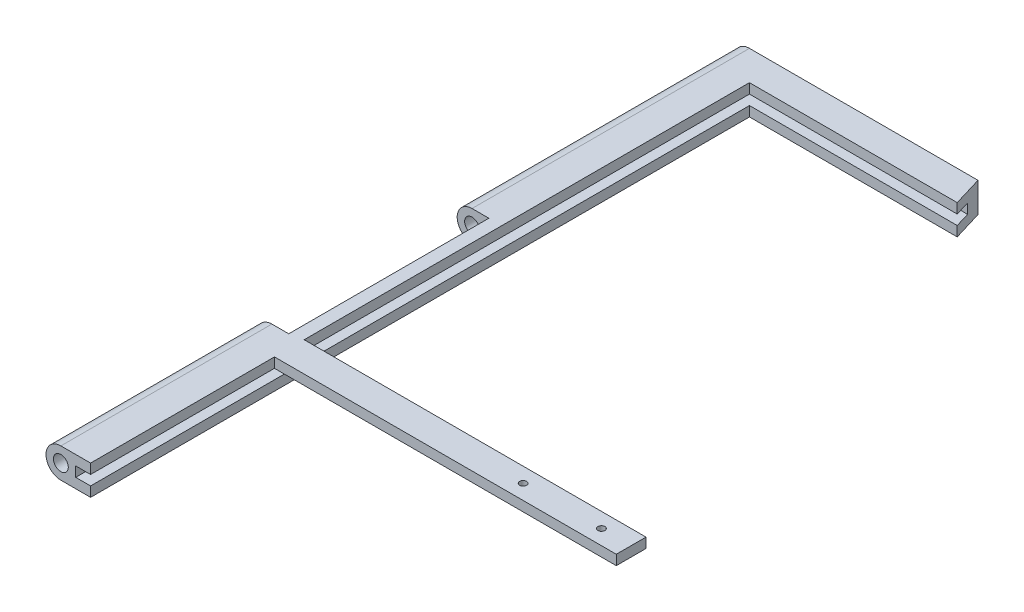
SolidWorks part; units mm, degrees
ref_plane "前视基准面" through (0, 0, 0) normal (0, 0, 1) x (1, 0, 0)
ref_plane "上视基准面" through (0, 0, 0) normal (0, 1, 0) x (1, 0, 0)
ref_plane "右视基准面" through (0, 0, 0) normal (1, 0, 0) x (0, 0, -1)
other "Configuration Table"
sketch "草图1" plane through (0, 0, 0) normal (0, 1, 0) x (1, 0, 0)
  line L0 (0, 0) -> (0, -73)
  line L1 (0, -73) -> (38.8, -73)
  line L2 (38.8, -73) -> (38.8, -47.5)
  line L3 (38.8, -47.5) -> (24.5, 0)
  line L4 (24.5, 0) -> (0, 0)
  dimension "D3" = 25.5
  dimension "D4" = 24.5
  dimension "D1" = 73
  dimension "D2" = 38.8
extrude "凸台-拉伸1" add sketch "草图1" along normal blind 3
sketch "草图2" plane through (0, 0, 0) normal (0, 0, -1) x (-1, 0, 0)
  line L0 (0.2, 0) -> (0.2, 3) construction
  line L1 (0, 0) -> (1.7, 0)
  line L2 (0, 0) -> (0, 3)
  line L3 (0, 3) -> (1.7, 3)
  line L4 (1.7, 0) -> (1.7, 3) construction
  circle A0 centre (1.7, 1.5) radius 1.5
  circle A1 centre (1.7, 1.5) radius 0.75
  line M10 (0, 0) -> (0, 3)
  dimension "D2" = 1.5
  dimension "D1" = 0.2
extrude "凸台-拉伸2" add sketch "草图2" against normal up to surface (73 mm away) contours A0 L3 L1 M10 | A0 A1 region at (-0.0345, 1.5, 0) region at (-0.2424, 1.5, 0) up to face at (19.4, 1.5, 73)
sketch "草图3" plane through (0, 3, 0) normal (0, 1, 0) x (1, 0, 0)
  line L0 (-1.7, -73) -> (38.8, -73) construction
  line L1 (38.8, -73) -> (-3.2, -73)
  line L2 (38.8, -73) -> (38.8, -69.5)
  line L3 (38.8, -69.5) -> (-3.2, -69.5)
  line L4 (-3.2, -73) -> (-3.2, -69.5)
  line L5 (38.8, -73) -> (38.8, -47.5) construction
  line L6 (-3.2, 0) -> (-3.2, -73) construction
  line L7 (-1.7, -73) -> (-1.7, 0) construction
  line L8 (0, -48.2) -> (-3.2, -48.2)
  line L9 (0, -48.2) -> (0, -28)
  line L10 (0, -28) -> (-3.2, -28)
  line L11 (-3.2, -48.2) -> (-3.2, -28)
  line L12 (-1.7, 0) -> (-3.2, 0) construction
  line L13 (1.3, -3) -> (22.2702, -3)
  line L14 (22.2702, -3) -> (35.8, -47.9418)
  line L15 (35.8, -47.9418) -> (35.8, -69.5)
  line L16 (35.8, -69.5) -> (1.3, -69.5)
  line L17 (1.3, -69.5) -> (1.3, -3)
  line L18 (38.8, -47.5) -> (24.5, 0) construction
  line L19 (24.5, 0) -> (-1.7, 0) construction
  dimension "D1" = 3.5
  dimension "D2" = 20.2
  dimension "D3" = 28
  dimension "D4" = 3
  dimension "D5" = 3
  dimension "D6" = 3
  dimension "D7" = 3
  dimension "D8" = 3.2
extrude "切除-拉伸1" cut sketch "草图3" against normal through all contours L17 L3 L15 L14 L13 | L11 L10 L9 L8 | L3 L4 L1 L2 region at (16.6038, 3, 39.0408)
sketch "草图4" plane through (1.3, 0, 0) normal (1, 0, 0) x (0, 0, -1)
  line L0 (-69.5, 0) -> (-69.5, 3) construction
  line L1 (-1.5, 1) -> (-69.5, 1)
  line L2 (-1.5, 1) -> (-1.5, 2)
  line L3 (-1.5, 2) -> (-69.5, 2)
  line L4 (-69.5, 1) -> (-69.5, 2)
  line L5 (-69.5, 0) -> (-47.5, 0) construction
  line L6 (-3, 0) -> (-3, 3) construction
  line L7 (-47.5, 2) -> (-47.5, 1)
  line L8 (-47.5, 3) -> (-47.5, 0) construction
  line M5 (-69.5, 3) -> (-69.5, 0)
  line M7 (-3, 0) -> (-3, 3)
  dimension "D1" = 1
  dimension "D2" = 1
  dimension "D3" = 1.5
extrude "切除-拉伸2" cut sketch "草图4" along normal offset from surface (24.0367 mm away) 1.5 from offset 1.5 contours L3 L7 L1 M7 region at (1.3, 1.5, 25.25) up to face at (29.0351, 1.5, 25.4709) offset beyond the face yes offset against normal yes
extrude "切除-拉伸3" cut sketch "草图4<3>" along normal offset from surface (37.5 mm away) 1.5 from offset 1.5 contours L7 L3 L1 M5 region at (1.3, 1.5, 58.5) up to face at (35.8, 1.5, 58.7209) offset beyond the face yes offset against normal yes
sketch "草图4<3>" plane through (1.3, 0, 0) normal (1, 0, 0) x (0, 0, -1) same geometry as "草图4"
sketch "草图5" plane through (35.8, 0, 0) normal (-1, 0, 0) x (0, 0, 1)
  line L0 (47.9418, 3) -> (69.5, 3) construction
  line L1 (47.9418, 3) -> (50.9418, 3)
  line L2 (47.9418, 3) -> (47.9418, 2)
  line L3 (47.9418, 2) -> (50.9418, 2)
  line L4 (50.9418, 3) -> (50.9418, 2)
  line L5 (47.9418, 2) -> (69.5, 2) construction
  line L6 (47.9418, 2) -> (47.9418, 3) construction
  dimension "D1" = 3
extrude "凸台-拉伸3" add sketch "草图5" along normal up to surface (34.5 mm away) up to face at (1.3, 2.5, 36.25)
sketch "草图6" plane through (0, 3, 0) normal (0, 1, 0) x (1, 0, 0)
  line L0 (35.8, -50.9418) -> (35.8, -47.9418) construction
  line L1 (35.8, -50.9418) -> (35.8, -69.5) construction
  line L2 (1.3, -50.9418) -> (35.8, -50.9418) construction
  line L3 (1.3, -47.9418) -> (35.8, -47.9418) construction
  circle A0 centre (32.8, -49.4418) radius 0.35
  circle A1 centre (24.9, -49.4418) radius 0.35
  point P14 (35.8, -49.4418)
  dimension "D1" = 0.7
  dimension "D2" = 7.9
  dimension "D3" = 3
extrude "切除-拉伸4" cut sketch "草图6" against normal through all
sketch "草图7" plane through (0, 0, 3) normal (0, 0, 1) x (1, 0, 0)
  line L0 (-0.2, 2) -> (-0.2, 1) construction
  line L1 (-0.2, 2) -> (23.8367, 2)
  line L2 (-0.2, 2) -> (-0.2, 1)
  line L3 (-0.2, 1) -> (23.8367, 1)
  line L4 (23.8367, 2) -> (23.8367, 1)
  line L5 (22.2702, 1) -> (35.8, 1) construction
  line L6 (1.3, 2) -> (35.8, 2) construction
  line L7 (23.8367, 2) -> (23.8367, 1) construction
extrude "切除-拉伸5" cut sketch "草图7" against normal blind 1.5
sketch "草图8" plane through (0, 3, 0) normal (0, 1, 0) x (1, 0, 0)
  line L0 (20.3324, 3.4367) -> (35.8, -47.9418)
  line L1 (35.8, -47.9418) -> (35.8, -72.8495)
  line L2 (35.8, -72.8495) -> (56.308, -72.8495)
  line L3 (56.308, -72.8495) -> (56.308, 3.4367)
  line L4 (56.308, 3.4367) -> (20.3324, 3.4367)
  line L5 (22.2702, -3) -> (35.8, -47.9418) construction
extrude "切除-拉伸6" cut sketch "草图8" against normal through all
